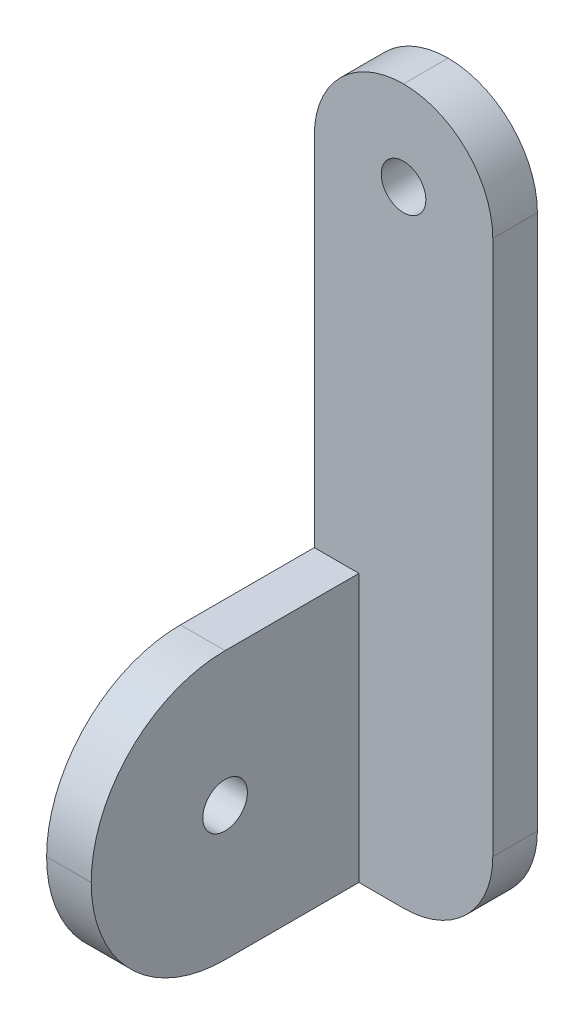
SolidWorks part; units mm, degrees
ref_plane "Plan de face" through (0, 0, 0) normal (0, 0, 1) x (1, 0, 0)
ref_plane "Plan de dessus" through (0, 0, 0) normal (0, 1, 0) x (1, 0, 0)
ref_plane "Plan de droite" through (0, 0, 0) normal (1, 0, 0) x (0, 0, -1)
sketch "Esquisse1" plane through (0, 0, 0) normal (0, 0, 1) x (1, 0, 0)
  line L1 (-43.6933, 39.2712) -> (-23.6933, 39.2712)
  line L2 (-43.6933, 39.2712) -> (-43.6933, -40.7288)
  line L3 (-43.6933, -40.7288) -> (-23.6933, -40.7288)
  line L4 (-23.6933, 39.2712) -> (-23.6933, -40.7288)
  dimension "D1" = 20
  dimension "D2" = 80
extrude "Boss.-Extru.1" add sketch "Esquisse1" along normal blind 5
sketch "Esquisse2" plane through (0, 0, 5) normal (0, 0, 1) x (1, 0, 0)
  line L0 (-23.6933, 39.2712) -> (-43.6933, 39.2712) construction
  line L2 (-43.6933, 39.2712) -> (-43.6933, -40.7288) construction
  circle A0 centre (-33.6933, 29.2712) radius 2.5
  dimension "D3" = 5
  dimension "D1" = 10
  dimension "D2" = 10
extrude "Enlèv. mat.-Extru.1" cut sketch "Esquisse2" against normal blind 5
sketch "Esquisse3" plane through (0, 0, 5) normal (0, 0, 1) x (1, 0, 0)
  line L1 (-43.6933, -40.7288) -> (-38.6933, -40.7288)
  line L2 (-43.6933, -40.7288) -> (-43.6933, -10.7288)
  line L3 (-43.6933, -10.7288) -> (-38.6933, -10.7288)
  line L4 (-38.6933, -40.7288) -> (-38.6933, -10.7288)
  dimension "D1" = 5
  dimension "D2" = 30
extrude "Boss.-Extru.2" add sketch "Esquisse3" along normal blind 30
sketch "Esquisse4" plane through (-43.6933, 0, 0) normal (-1, 0, 0) x (0, 0, 1)
  line L0 (35, -10.7288) -> (5, -10.7288) construction
  line L1 (35, -10.7288) -> (35, -40.7288) construction
  circle A0 centre (20, -25.7288) radius 2.5
  dimension "D2" = 5
  dimension "D1" = 15
  dimension "D3" = 15
extrude "Enlèv. mat.-Extru.2" cut sketch "Esquisse4" against normal blind 30
fillet "Congé1" radius 15 2 edges at (-41.1933, -40.7288, 35) (-41.1933, -10.7288, 35)
fillet "Congé2" radius 10 3 edges at (-23.6933, -40.7288, 2.5) (-23.6933, 39.2712, 2.5) (-43.6933, 39.2712, 2.5)
